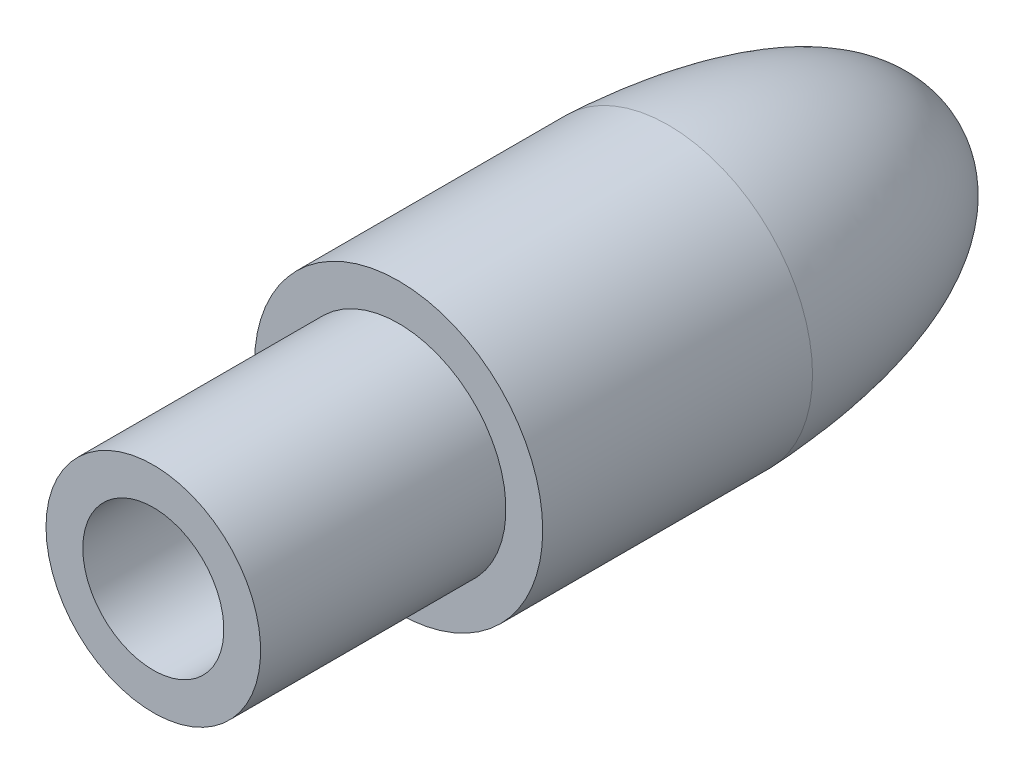
SolidWorks part; units mm, degrees
ref_plane "Front Plane" through (0, 0, 0) normal (0, 0, 1) x (1, 0, 0)
ref_plane "Top Plane" through (0, 0, 0) normal (0, 1, 0) x (1, 0, 0)
ref_plane "Right Plane" through (0, 0, 0) normal (1, 0, 0) x (0, 0, -1)
sketch "Sketch1" plane through (0, 0, 0) normal (0, 1, 0) x (1, 0, 0)
  line L0 (0, 11.4224) -> (0, 8.9224)
  line L3 (-11.75, -10.5776) -> (-11.75, -32.5776)
  line L4 (-11.75, -32.5776) -> (-8.75, -32.5776)
  line L5 (-8.75, -32.5776) -> (-8.75, -52.5776)
  line L6 (-8.75, -52.5776) -> (-5.75, -52.5776)
  line L7 (-5.75, -52.5776) -> (-5.75, -29.5776)
  line L8 (-5.75, -29.5776) -> (-8.75, -29.5776)
  line L9 (-8.75, -29.5776) -> (-8.75, -10.5776)
  line L10 (-8.75, -10.5776) -> (0, 8.9224)
  spline S0 degree 3 poles (0, 11.4224) (-9.5108, 11.0416) (-11.3797, -3.0564) (-11.75, -10.5776) knots 0 0 0 0 1 1 1 1
  dimension "D2" = 8.75
  dimension "D1" = 2.5
  dimension "D3" = 44
  dimension "D4" = 22
  dimension "D5" = 3
  dimension "D6" = 20
  dimension "D7" = 3
  dimension "D8" = 23
revolve "Revolve1" add sketch "Sketch1" angle 360 about L0
